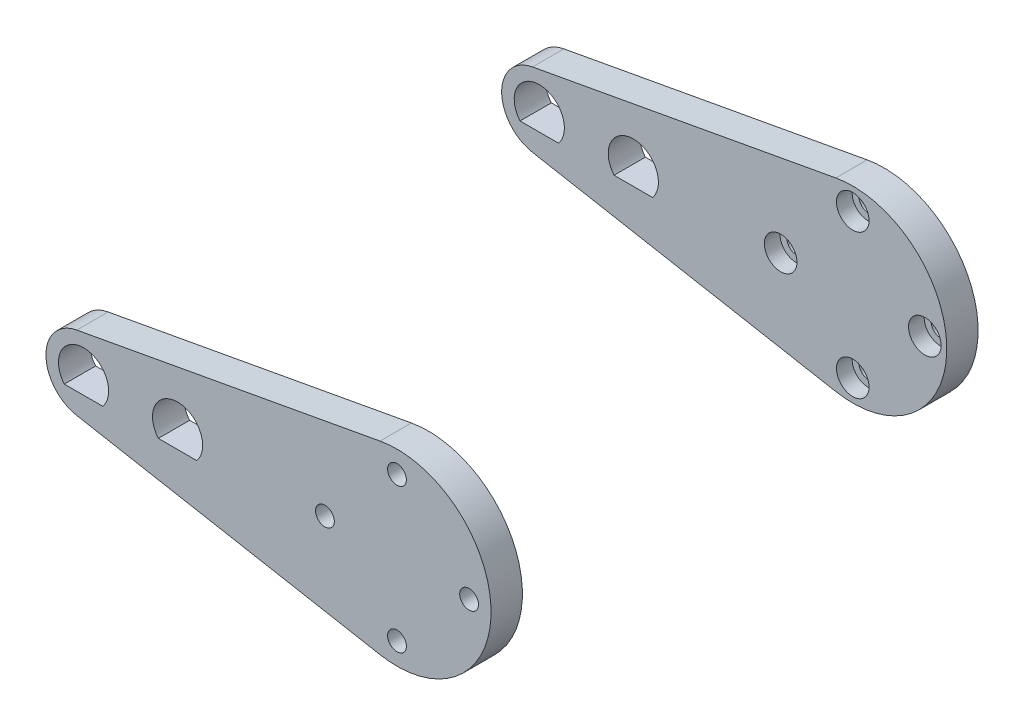
SolidWorks part; units mm, degrees
ref_plane "Front Plane" through (0, 0, 0) normal (0, 0, 1) x (1, 0, 0)
ref_plane "Top Plane" through (0, 0, 0) normal (0, 1, 0) x (1, 0, 0)
ref_plane "Right Plane" through (0, 0, 0) normal (1, 0, 0) x (0, 0, -1)
sketch "Sketch1" plane through (0, 0, 0) normal (0, 0, 1) x (1, 0, 0)
  circle A0 centre (0, 0) radius 15
  circle A1 centre (0, 0) radius 11.5 construction
  circle A2 centre (0, 11.5) radius 2.6
  circle A3 centre (11.5, 0) radius 2.6
  circle A4 centre (0, -11.5) radius 2.6
  circle A5 centre (-11.5, 0) radius 2.6
  circle A6 centre (0, 11.5) radius 1.5
  circle A7 centre (11.5, 0) radius 1.5
  circle A8 centre (0, -11.5) radius 1.5
  circle A9 centre (-11.5, 0) radius 1.5
  point P15 (0, 0)
  point P23 (0, 0)
  dimension "D1" = 30
  dimension "D2" = 23
  dimension "D3" = 5.2
  dimension "D5" = 3
  dimension "D4" = 4
  dimension "D6" = 4
extrude "Boss-Extrude1" add sketch "Sketch1" along normal blind 5 contours A0 A5 A4 A3 A2 region at (0, 0, 0)
extrude "Boss-Extrude2" add sketch "Sketch1<3>" along normal blind 2.5 contours A2 A6 | A5 A9 | A4 A8 | A3 A7 region at (-2.5265, 11.5, 0) region at (8.9735, 0, 0) region at (-2.5265, -11.5, 0) region at (-14.0265, 0, 0)
sketch "Sketch1<3>" plane through (0, 0, 0) normal (0, 0, 1) x (1, 0, 0) same geometry as "Sketch1"
sketch "Sketch2" plane through (0, 0, 0) normal (0, 0, 1) x (1, 0, 0)
  line L0 (0, 0) -> (-58.5269, 0) construction
  line L1 (-51.08, 5.902) -> (-2.7, 14.755)
  line L2 (-51.08, -5.902) -> (-2.7, -14.755)
  line L7 (-53.075, -2.5582) -> (-46.925, -2.5582)
  line L8 (-53.075, -2.5582) -> (-8.6522, -2.5582) construction
  line L9 (-38.075, -2.5582) -> (-31.925, -2.5582)
  arc A0 (-46.925, -2.5582) -> (-53.075, -2.5582) centre (-50, 0) ccw
  arc A1 (-51.08, 5.902) -> (-51.08, -5.902) centre (-50, 0) ccw
  circle A3 centre (0, 0) radius 15 construction
  arc A4 (-31.925, -2.5582) -> (-38.075, -2.5582) centre (-35, 0) ccw
  circle A9 centre (0, 0) radius 15
  arc A10 (-16.925, -2.5582) -> (-23.075, -2.5582) centre (-20, 0) ccw [skipped]
  dimension "D2" = 8
  dimension "D3" = 12
  dimension "D6" = 3
  dimension "D7" = 6.15
  dimension "D1" = 50
extrude "Boss-Extrude3" add sketch "Sketch2" along normal blind 5 contours L1 A1 L2 A4 L9 A0 L7 region at (-29.1063, -0.0568, 0)
ref_plane "Plane1" through (0, 0, 38.848) normal (0, 0, 1) x (1, 0, 0)
mirror "Mirror2" about plane through (0, 0, 38.848) normal (0, 0, 1) of bodies 103
